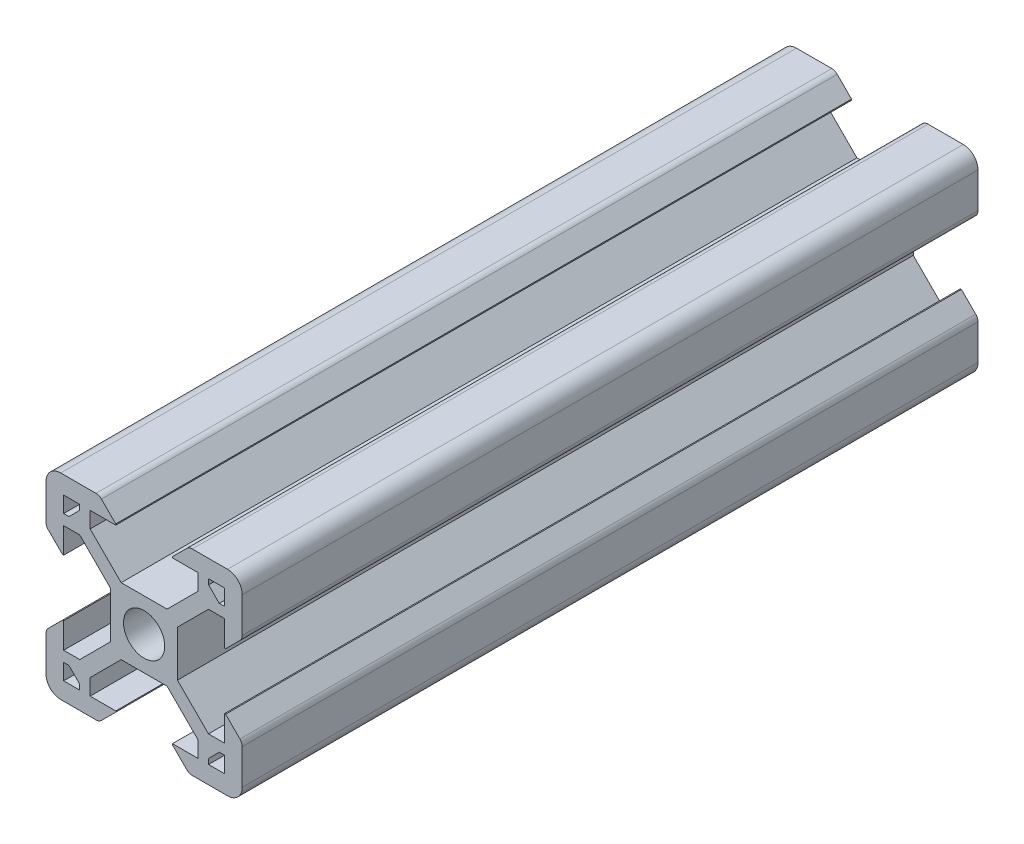
SolidWorks part; units mm, degrees
ref_plane "Front Plane" through (0, 0, 0) normal (0, 0, 1) x (1, 0, 0)
ref_plane "Top Plane" through (0, 0, 0) normal (0, 1, 0) x (1, 0, 0)
ref_plane "Right Plane" through (0, 0, 0) normal (1, 0, 0) x (0, 0, -1)
sketch "Sketch2" plane through (0, 0, 0) normal (0, 0, 1) x (1, 0, 0)
  line L0 (-8.2, 2.89) -> (-8.2, 5.5)
  line L1 (-2.1, 0) -> (-10, 0) construction
  line L2 (0, 2.1) -> (0, 10) construction
  line L3 (-4.9072, 10) -> (-8.5, 10)
  line L4 (-10, 4.9072) -> (-10, 8.5)
  line L5 (-2.1, 0) -> (-3.4, 0) construction
  line L6 (0, 2.1) -> (0, 3.4) construction
  line L7 (0, 3.4) -> (-2.3393, 3.4)
  line L8 (-3.4, 0) -> (-3.4, 2.3393)
  line L9 (-2.89, 8.2) -> (-5.5, 8.2)
  line L10 (-6.57, 8.2) -> (-6.57, 7.66)
  line L11 (-8.2, 6.57) -> (-7.66, 6.57)
  line L12 (-5.5, 8.2) -> (-5.5, 6.5607)
  line L13 (-6.5607, 5.5) -> (-8.2, 5.5)
  line L14 (-8.2, 8.2) -> (-1.4849, 1.4849) construction
  line L15 (-6.5607, 5.5) -> (-3.4, 2.3393)
  line L16 (-5.5, 6.5607) -> (-2.3393, 3.4)
  line L17 (-7.66, 6.57) -> (-6.57, 7.66)
  line L18 (-8.7303, 7.6697) -> (-0.5303, -0.5303) construction
  line L19 (-7.6697, 8.7303) -> (0.5303, 0.5303) construction
  line L20 (-8.2, 8.2) -> (0, 0) construction
  line L21 (-8.2, 6.57) -> (-8.2, 8.2)
  line L22 (-8.2, 0) -> (-8.2, 8.2) construction
  line L23 (-6.57, 8.2) -> (-8.2, 8.2)
  line L24 (0, 8.2) -> (-8.2, 8.2) construction
  line L25 (-10, 0) -> (-10, 10) construction
  line L26 (0, 10) -> (-10, 10) construction
  line L27 (-2.89, 8.31) -> (-2.89, 8.2)
  line L29 (-8.31, 2.89) -> (-8.2, 2.89)
  line L30 (-4.3486, 9.7686) -> (-2.89, 8.31)
  line L31 (-8.31, 2.89) -> (-9.7686, 4.3486)
  arc A0 (0, 2.1) -> (-2.1, 0) centre (0, 0) ccw
  arc A1 (-10, 8.5) -> (-8.5, 10) centre (-8.5, 8.5) cw
  arc A2 (-9.7686, 4.3486) -> (-10, 4.9072) centre (-9.21, 4.9072) cw
  arc A3 (-4.3486, 9.7686) -> (-4.9072, 10) centre (-4.9072, 9.21) ccw
  point P29 (-10, 10)
  point P39 (-10, 4.58)
  point P42 (-4.58, 10)
  dimension "D3" = 2.1
  dimension "D15" = 1.5
  dimension "D22" = 0.79
  dimension "D1" = 10
  dimension "D2" = 10
  dimension "D4" = 1.8
  dimension "D5" = 3.43
  dimension "D6" = 3.43
  dimension "D7" = 0.54
  dimension "D8" = 0.54
  dimension "D9" = 1.07
  dimension "D10" = 1.07
  dimension "D11" = 3.4
  dimension "D12" = 3.4
  dimension "D16" = 7.11
  dimension "D17" = 0.11
  dimension "D18" = 1.69
  dimension "D19" = 0.11
  dimension "D20" = 7.11
  dimension "D21" = 1.69
  dimension "D13" = 0.75
  dimension "D14" = 0.75
sketch "Sketch6" plane through (0, 0, 0) normal (0, 0, 1) x (1, 0, 0)
  line L0 (-3.4, 0) -> (-3.4, 2.3393) construction
  line L1 (-6.5607, 5.5) -> (-3.4, 2.3393) construction
  line L2 (-6.5607, 5.5) -> (-8.2, 5.5) construction
  line L3 (-8.2, 2.89) -> (-8.2, 5.5) construction
  line L4 (-8.31, 2.89) -> (-8.2, 2.89) construction
  line L5 (-7.66, 6.57) -> (-6.57, 7.66)
  line L6 (-6.57, 7.66) -> (-6.57, 8.2)
  line L7 (-6.57, 8.2) -> (-8.2, 8.2)
  line L8 (-8.2, 8.2) -> (-8.2, 6.57)
  line L9 (-8.2, 6.57) -> (-7.66, 6.57)
  line L10 (-7.66, 6.57) -> (-6.57, 7.66)
  line L11 (-6.57, 7.66) -> (-6.57, 8.2)
  line L12 (-6.57, 8.2) -> (-8.2, 8.2)
  line L13 (-8.2, 8.2) -> (-8.2, 6.57)
  line L14 (-8.2, 6.57) -> (-7.66, 6.57)
  line L15 (-8.31, 2.89) -> (-9.7686, 4.3486) construction
  line L16 (-10, 4.9072) -> (-10, 8.5) construction
  line L17 (-4.9072, 10) -> (-8.5, 10) construction
  line L18 (-4.3486, 9.7686) -> (-2.89, 8.31) construction
  line L19 (-2.89, 8.31) -> (-2.89, 8.2) construction
  line L20 (-2.89, 8.2) -> (-5.5, 8.2) construction
  line L21 (-5.5, 8.2) -> (-5.5, 6.5607) construction
  line L22 (-5.5, 6.5607) -> (-2.3393, 3.4) construction
  line L23 (0, 3.4) -> (-2.3393, 3.4) construction
  line L24 (-3.4, -2.3393) -> (-3.4, 2.3393)
  line L25 (-6.5607, 5.5) -> (-3.4, 2.3393)
  line L26 (-6.5607, 5.5) -> (-8.2, 5.5)
  line L27 (-8.2, 2.89) -> (-8.2, 5.5)
  line L28 (-8.31, 2.89) -> (-8.2, 2.89)
  line L29 (-8.31, 2.89) -> (-9.7686, 4.3486)
  line L30 (-10, 4.9072) -> (-10, 8.5)
  line L31 (-4.9072, 10) -> (-8.5, 10)
  line L32 (-4.3486, 9.7686) -> (-2.89, 8.31)
  line L33 (-2.89, 8.31) -> (-2.89, 8.2)
  line L34 (-2.89, 8.2) -> (-5.5, 8.2)
  line L35 (-5.5, 8.2) -> (-5.5, 6.5607)
  line L36 (-5.5, 6.5607) -> (-2.3393, 3.4)
  line L37 (2.3393, 3.4) -> (-2.3393, 3.4)
  line L38 (0, 2.1) -> (0, 10) construction
  line L39 (-2.1, 0) -> (-10, 0) construction
  line L40 (0, 2.1) -> (0, 10) construction
  line L41 (-2.1, 0) -> (-10, 0) construction
  line L42 (2.1, 0) -> (10, 0) construction
  line L43 (5.5, 6.5607) -> (2.3393, 3.4)
  line L44 (5.5, 8.2) -> (5.5, 6.5607)
  line L45 (2.89, 8.2) -> (5.5, 8.2)
  line L46 (2.89, 8.31) -> (2.89, 8.2)
  line L47 (4.3486, 9.7686) -> (2.89, 8.31)
  line L48 (4.9072, 10) -> (8.5, 10)
  line L49 (10, 4.9072) -> (10, 8.5)
  line L50 (8.31, 2.89) -> (9.7686, 4.3486)
  line L51 (8.31, 2.89) -> (8.2, 2.89)
  line L52 (8.2, 2.89) -> (8.2, 5.5)
  line L53 (6.5607, 5.5) -> (8.2, 5.5)
  line L54 (6.5607, 5.5) -> (3.4, 2.3393)
  line L55 (3.4, -2.3393) -> (3.4, 2.3393)
  line L56 (8.2, 6.57) -> (7.66, 6.57)
  line L57 (8.2, 8.2) -> (8.2, 6.57)
  line L58 (6.57, 8.2) -> (8.2, 8.2)
  line L59 (6.57, 7.66) -> (6.57, 8.2)
  line L60 (7.66, 6.57) -> (6.57, 7.66)
  line L61 (0, -2.1) -> (0, -10) construction
  line L62 (7.66, -6.57) -> (6.57, -7.66)
  line L63 (6.57, -7.66) -> (6.57, -8.2)
  line L64 (6.57, -8.2) -> (8.2, -8.2)
  line L65 (8.2, -8.2) -> (8.2, -6.57)
  line L66 (8.2, -6.57) -> (7.66, -6.57)
  line L67 (6.5607, -5.5) -> (3.4, -2.3393)
  line L68 (6.5607, -5.5) -> (8.2, -5.5)
  line L69 (8.2, -2.89) -> (8.2, -5.5)
  line L70 (8.31, -2.89) -> (8.2, -2.89)
  line L71 (8.31, -2.89) -> (9.7686, -4.3486)
  line L72 (10, -4.9072) -> (10, -8.5)
  line L73 (4.9072, -10) -> (8.5, -10)
  line L74 (4.3486, -9.7686) -> (2.89, -8.31)
  line L75 (2.89, -8.31) -> (2.89, -8.2)
  line L76 (2.89, -8.2) -> (5.5, -8.2)
  line L77 (5.5, -8.2) -> (5.5, -6.5607)
  line L78 (5.5, -6.5607) -> (2.3393, -3.4)
  line L79 (2.3393, -3.4) -> (-2.3393, -3.4)
  line L80 (-5.5, -6.5607) -> (-2.3393, -3.4)
  line L81 (-5.5, -8.2) -> (-5.5, -6.5607)
  line L82 (-2.89, -8.2) -> (-5.5, -8.2)
  line L83 (-2.89, -8.31) -> (-2.89, -8.2)
  line L84 (-4.3486, -9.7686) -> (-2.89, -8.31)
  line L85 (-4.9072, -10) -> (-8.5, -10)
  line L86 (-10, -4.9072) -> (-10, -8.5)
  line L87 (-8.31, -2.89) -> (-9.7686, -4.3486)
  line L88 (-8.31, -2.89) -> (-8.2, -2.89)
  line L89 (-8.2, -2.89) -> (-8.2, -5.5)
  line L90 (-6.5607, -5.5) -> (-8.2, -5.5)
  line L91 (-6.5607, -5.5) -> (-3.4, -2.3393)
  line L92 (-8.2, -6.57) -> (-7.66, -6.57)
  line L93 (-8.2, -8.2) -> (-8.2, -6.57)
  line L94 (-6.57, -8.2) -> (-8.2, -8.2)
  line L95 (-6.57, -7.66) -> (-6.57, -8.2)
  line L96 (-7.66, -6.57) -> (-6.57, -7.66)
  arc A0 (0, 2.1) -> (-2.1, 0) centre (0, 0) ccw construction
  arc A1 (-10, 4.9072) -> (-9.7686, 4.3486) centre (-9.21, 4.9072) ccw construction
  arc A2 (-8.5, 10) -> (-10, 8.5) centre (-8.5, 8.5) ccw construction
  arc A3 (-4.3486, 9.7686) -> (-4.9072, 10) centre (-4.9072, 9.21) ccw construction
  circle A4 centre (0, 0) radius 2.1
  arc A5 (-10, 4.9072) -> (-9.7686, 4.3486) centre (-9.21, 4.9072) ccw
  arc A6 (-8.5, 10) -> (-10, 8.5) centre (-8.5, 8.5) ccw
  arc A7 (-4.3486, 9.7686) -> (-4.9072, 10) centre (-4.9072, 9.21) ccw
  arc A8 (4.3486, 9.7686) -> (4.9072, 10) centre (4.9072, 9.21) cw
  arc A9 (8.5, 10) -> (10, 8.5) centre (8.5, 8.5) cw
  arc A10 (10, 4.9072) -> (9.7686, 4.3486) centre (9.21, 4.9072) cw
  arc A11 (10, -4.9072) -> (9.7686, -4.3486) centre (9.21, -4.9072) ccw
  arc A12 (8.5, -10) -> (10, -8.5) centre (8.5, -8.5) ccw
  arc A13 (4.3486, -9.7686) -> (4.9072, -10) centre (4.9072, -9.21) ccw
  arc A14 (-4.3486, -9.7686) -> (-4.9072, -10) centre (-4.9072, -9.21) cw
  arc A15 (-8.5, -10) -> (-10, -8.5) centre (-8.5, -8.5) cw
  arc A16 (-10, -4.9072) -> (-9.7686, -4.3486) centre (-9.21, -4.9072) cw
  point P85 (3.4, 0)
  dimension "D1" = 0
extrude "Boss-Extrude1" add sketch "Sketch6" against normal blind 75
